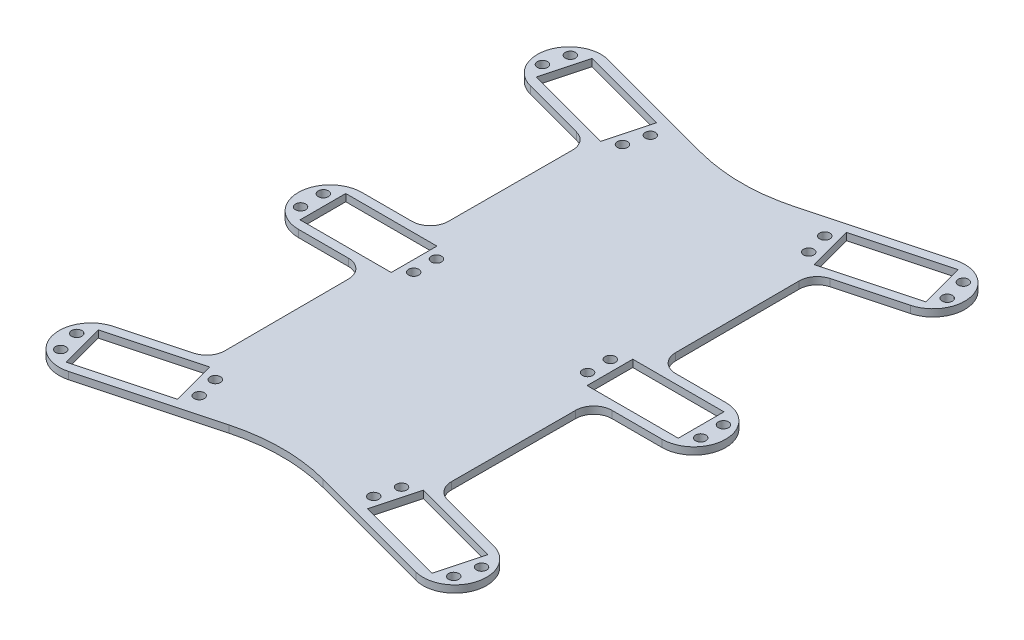
SolidWorks part; units mm, degrees
ref_plane "Front Plane" through (0, 0, 0) normal (0, 0, 1) x (1, 0, 0)
ref_plane "Top Plane" through (0, 0, 0) normal (0, 1, 0) x (1, 0, 0)
ref_plane "Right Plane" through (0, 0, 0) normal (1, 0, 0) x (0, 0, -1)
sketch "Sketch1" plane through (0, 0, 0) normal (0, 1, 0) x (1, 0, 0)
  line L0 (0, 32.1883) -> (0, -21.4181) construction
  line L1 (0, 0) -> (27.1703, 0) construction
  line L2 (-80, 14) -> (-50, 14)
  line L3 (-50, 14) -> (-49.8161, 82.5959)
  line L4 (-49.8161, 82.5959) -> (-83.6235, 91.6546)
  line L5 (-76.3765, 118.7005) -> (0, 98.2355)
  line L10 (-76.3765, 118.7005) -> (-83.6235, 91.6546) construction
  line L12 (-80, 14) -> (-80, -14) construction
  line L14 (-76.3765, -118.7005) -> (0, -98.2355)
  line L15 (-49.8161, -82.5959) -> (-83.6235, -91.6546)
  line L16 (-50, -14) -> (-49.8161, -82.5959)
  line L17 (-80, -14) -> (-50, -14)
  line L18 (76.3765, -118.7005) -> (0, -98.2355)
  line L19 (76.3765, 118.7005) -> (0, 98.2355)
  line L20 (80, 14) -> (80, -14) construction
  line L21 (76.3765, 118.7005) -> (83.6235, 91.6546) construction
  line L22 (80, -14) -> (50, -14)
  line L23 (50, -14) -> (49.8161, -82.5959)
  line L24 (49.8161, -82.5959) -> (83.6235, -91.6546)
  line L25 (49.8161, 82.5959) -> (83.6235, 91.6546)
  line L26 (50, 14) -> (49.8161, 82.5959)
  line L27 (80, 14) -> (50, 14)
  line L28 (-80.4609, 115.7056) -> (-85.6631, 96.2905)
  line L29 (-85.6631, 96.2905) -> (-46.9295, 85.9118)
  line L30 (-46.9295, 85.9118) -> (-41.7272, 105.3269)
  line L31 (-41.7272, 105.3269) -> (-80.4609, 115.7056)
  line L32 (-61.094, 110.5162) -> (-66.2963, 91.1011) construction
  line L33 (-80, 105.1776) -> (-83.062, 105.998) construction
  line L34 (-63.12, 10.05) -> (-63.12, -10.05) construction
  line L35 (-83.17, 10.05) -> (-43.07, 10.05)
  line L36 (-83.17, 10.05) -> (-83.17, -10.05)
  line L37 (-83.17, -10.05) -> (-43.07, -10.05)
  line L38 (-43.07, 10.05) -> (-43.07, -10.05)
  line L39 (-83.17, 10.05) -> (-43.07, -10.05) construction
  line L40 (-83.17, -10.05) -> (-43.07, 10.05) construction
  line L41 (-46.9295, -85.9118) -> (-41.7272, -105.3269)
  line L42 (-41.7272, -105.3269) -> (-80.4609, -115.7056)
  line L43 (-80.4609, -115.7056) -> (-85.6631, -96.2905)
  line L44 (-85.6631, -96.2905) -> (-46.9295, -85.9118)
  line L45 (46.9295, 85.9118) -> (41.7272, 105.3269)
  line L46 (85.6631, 96.2905) -> (46.9295, 85.9118)
  line L47 (80.4609, 115.7056) -> (85.6631, 96.2905)
  line L48 (41.7272, 105.3269) -> (80.4609, 115.7056)
  line L49 (83.17, -10.05) -> (43.07, 10.05) construction
  line L50 (83.17, 10.05) -> (43.07, -10.05) construction
  line L51 (63.12, 10.05) -> (63.12, -10.05) construction
  line L52 (43.07, 10.05) -> (43.07, -10.05)
  line L53 (83.17, -10.05) -> (43.07, -10.05)
  line L54 (83.17, 10.05) -> (83.17, -10.05)
  line L55 (83.17, 10.05) -> (43.07, 10.05)
  line L56 (46.9295, -85.9118) -> (41.7272, -105.3269)
  line L57 (85.6631, -96.2905) -> (46.9295, -85.9118)
  line L58 (41.7272, -105.3269) -> (80.4609, -115.7056)
  line L59 (80.4609, -115.7056) -> (85.6631, -96.2905)
  line L60 (-86.4333, 112.0777) -> (-89.0215, 102.4185) construction
  line L61 (-87.7274, 107.2481) -> (-80, 105.1776) construction
  line L62 (-88, 5) -> (-88, -5) construction
  arc A0 (-80, 14) -> (-80, -14) centre (-80, 0) ccw
  arc A1 (-76.3765, 118.7005) -> (-83.6235, 91.6546) centre (-80, 105.1776) ccw
  circle A8 centre (-86.4333, 112.0777) radius 2.25
  circle A9 centre (-89.0215, 102.4185) radius 2.25
  circle A10 centre (-88, 5) radius 2.25
  arc A11 (-76.3765, -118.7005) -> (-83.6235, -91.6546) centre (-80, -105.1776) cw
  circle A12 centre (-89.0215, -102.4185) radius 2.25
  circle A13 centre (-86.4333, -112.0777) radius 2.25
  circle A14 centre (-88, -5) radius 2.25
  circle A15 centre (88, -5) radius 2.25
  circle A16 centre (86.4333, -112.0777) radius 2.25
  circle A17 centre (89.0215, -102.4185) radius 2.25
  arc A18 (76.3765, -118.7005) -> (83.6235, -91.6546) centre (80, -105.1776) ccw
  circle A19 centre (88, 5) radius 2.25
  circle A20 centre (89.0215, 102.4185) radius 2.25
  circle A21 centre (86.4333, 112.0777) radius 2.25
  arc A22 (76.3765, 118.7005) -> (83.6235, 91.6546) centre (80, 105.1776) cw
  arc A23 (80, 14) -> (80, -14) centre (80, 0) cw
  circle A24 centre (-40.957, 89.5396) radius 2.25
  circle A25 centre (-38.3688, 99.1989) radius 2.25
  circle A26 centre (-38.24, -5) radius 2.25
  circle A27 centre (-38.24, 5) radius 2.25
  circle A28 centre (-38.3688, -99.1989) radius 2.25
  circle A29 centre (-40.957, -89.5396) radius 2.25
  circle A30 centre (38.3688, 99.1989) radius 2.25
  circle A31 centre (40.957, 89.5396) radius 2.25
  circle A32 centre (38.24, 5) radius 2.25
  circle A33 centre (38.24, -5) radius 2.25
  circle A34 centre (40.957, -89.5396) radius 2.25
  circle A35 centre (38.3688, -99.1989) radius 2.25
  point P60 (-61.094, 110.5162)
  point P62 (-66.2963, 91.1011)
  point P65 (-83.062, 105.998)
  point P71 (-63.12, 0)
  point P108 (63.12, 0)
  point P118 (-93.523, 108.801)
  dimension "D2" = 14
  dimension "D3" = 10
  dimension "D8" = 4.5
  dimension "D1" = 75
  dimension "D4" = 80
  dimension "D5" = 30
  dimension "D6" = 35
  dimension "D7" = 68.5959
  dimension "D9" = 8
  dimension "D10" = 5
  dimension "D11" = 10
  dimension "D12" = 40.1
  dimension "D13" = 20.1
  dimension "D14" = 4.83
  dimension "D15" = 40.1
  dimension "D16" = 20.1
  dimension "D17" = 4.83
  dimension "D18" = 8
extrude "Boss-Extrude1" add sketch "Sketch1" along normal blind 3.175
fillet "Fillet1" radius 80 2 edges at (0, 1.5875, -98.2355) (0, 1.5875, 98.2355)
fillet "Fillet2" radius 8 8 edges at (49.8161, 1.5875, 82.5959) (50, 1.5875, 14) (50, 1.5875, -14) (49.8161, 1.5875, -82.5959) (-49.8161, 1.5875, -82.5959) (-50, 1.5875, -14) (-50, 1.5875, 14) (-49.8161, 1.5875, 82.5959)
